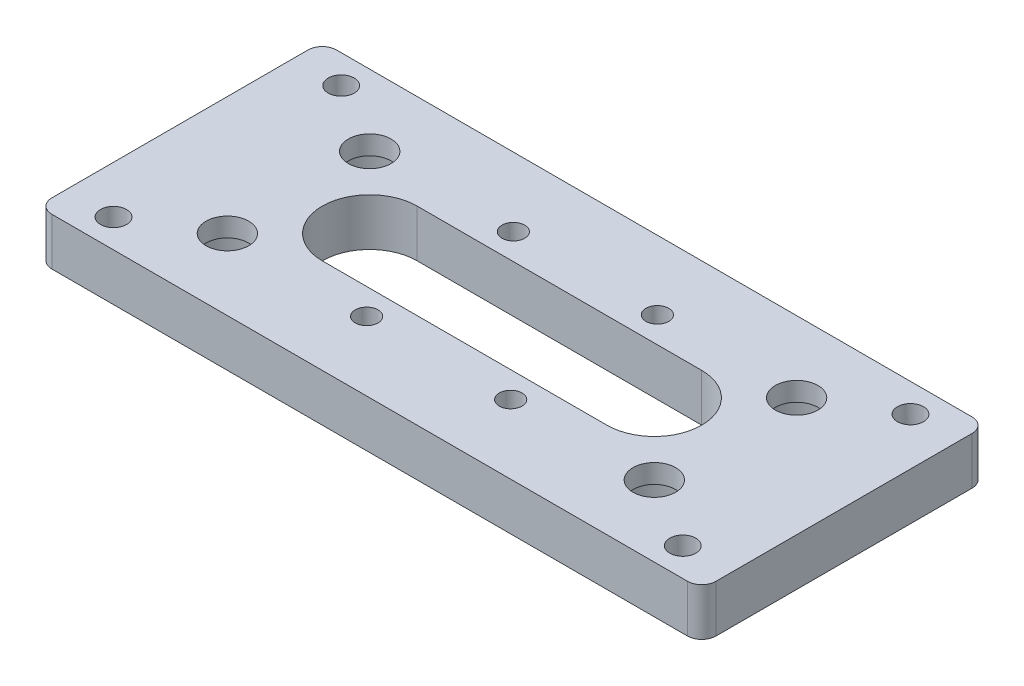
SolidWorks part; units mm, degrees
note: The reader was unsure of these and kept them because the rebuilt part matched: shared geometry of "Sketch1<2>".
ref_plane "Front Plane" through (0, 0, 0) normal (0, 0, 1) x (1, 0, 0)
ref_plane "Top Plane" through (0, 0, 0) normal (0, 1, 0) x (1, 0, 0)
ref_plane "Right Plane" through (0, 0, 0) normal (1, 0, 0) x (0, 0, -1)
sketch "Sketch1" plane through (0, 0, 0) normal (0, 1, 0) x (1, 0, 0)
  line L0 (65, -19) -> (65, 19) construction
  line L1 (-65, -19) -> (65, -19) construction
  line L2 (-65, 19) -> (-65, -19) construction
  line L3 (65, 19) -> (-65, 19) construction
  line L4 (67, 30) -> (-67, 30)
  line L5 (-70, 27) -> (-70, -27)
  line L6 (-67, -30) -> (67, -30)
  line L7 (70, -27) -> (70, 27)
  line L8 (67, 30) -> (-67, 30)
  line L9 (-70, 27) -> (-70, -27)
  line L10 (-67, -30) -> (67, -30)
  line L11 (70, -27) -> (70, 27)
  line L12 (65, -19) -> (65, 19)
  line L13 (-65, -19) -> (65, -19)
  line L14 (-65, 19) -> (-65, -19)
  line L15 (65, 19) -> (-65, 19)
  circle A0 centre (-60, 24) radius 2.75 construction
  circle A1 centre (-60, -24) radius 2.75 construction
  circle A2 centre (60, -24) radius 2.75 construction
  circle A3 centre (60, 24) radius 2.75 construction
  arc A4 (-67, 30) -> (-70, 27) centre (-67, 27) ccw
  arc A5 (-70, -27) -> (-67, -30) centre (-67, -27) ccw
  arc A6 (67, -30) -> (70, -27) centre (67, -27) ccw
  arc A7 (70, 27) -> (67, 30) centre (67, 27) ccw
  arc A8 (-67, 30) -> (-70, 27) centre (-67, 27) ccw
  arc A9 (-70, -27) -> (-67, -30) centre (-67, -27) ccw
  arc A10 (67, -30) -> (70, -27) centre (67, -27) ccw
  arc A11 (70, 27) -> (67, 30) centre (67, 27) ccw
  circle A12 centre (-60, 24) radius 2.75
  circle A13 centre (-60, -24) radius 2.75
  circle A14 centre (60, -24) radius 2.75
  circle A15 centre (60, 24) radius 2.75
  dimension "D1" = 0
extrude "Boss-Extrude1" add sketch "Sketch1" along normal blind 10
extrude "Boss-Extrude2" add sketch "Sketch1<2>" along normal blind 10
sketch "Sketch1<2>" plane through (0, 0, 0) normal (0, 1, 0) x (1, 0, 0) same geometry as "Sketch1"
hole_wizard "M3.5 Clearance Hole1" positions "Sketch2" profile "Sketch4" hole size "M3.5" standard "ANSI Metric"
sketch "Sketch2" plane through (0, 10, 0) normal (0, 1, 0) x (1, 0, 0)
  line L1 (15.1818, 15.4632) -> (-15.1818, 15.4632)
  line L2 (15.1818, 15.4632) -> (15.1818, -15.4632)
  line L3 (15.1818, -15.4632) -> (-15.1818, -15.4632)
  line L4 (-15.1818, 15.4632) -> (-15.1818, -15.4632)
  line L5 (15.1818, 15.4632) -> (-15.1818, -15.4632) construction
  line L6 (15.1818, -15.4632) -> (-15.1818, 15.4632) construction
  point P0 (0, 0)
  point P1 (-15.1818, -15.4632)
  point P16 (15.1818, 15.4632)
  point P17 (15.1818, -15.4632)
  point P18 (-15.1818, 15.4632)
sketch "Sketch4" plane through (0, 10, 0) normal (1, 0, 0) x (0, 0, 1)
  line L0 (0, 0) -> (0, 9.4421)
  line L1 (0, 9.4421) -> (2.4, 8)
  line L2 (2.4, 8) -> (2.4, 0)
  line L5 (2.4, 0) -> (0, 0)
  line L10 (0, 9.4421) -> (-2.4, 8) construction
  line L11 (0, -6.35) -> (0, 107.95) construction
  dimension "Hole Dia." = 4.8
  dimension "Hole Depth" = 8
  dimension "Drill Angle" = 118
sketch "Sketch5" plane through (0, 10, 0) normal (0, 1, 0) x (1, 0, 0)
  line L1 (-22.5, 22.5) -> (22.5, 22.5)
  line L2 (-22.5, 22.5) -> (-22.5, -22.5)
  line L3 (-22.5, -22.5) -> (22.5, -22.5)
  line L4 (22.5, 22.5) -> (22.5, -22.5)
  line L5 (-22.5, 22.5) -> (22.5, -22.5) construction
  line L6 (-22.5, -22.5) -> (22.5, 22.5) construction
  point P0 (0, 0)
  dimension "D1" = 45
  dimension "D2" = 45
sketch "Sketch6" plane through (0, 10, 0) normal (0, 1, 0) x (1, 0, 0)
  line L0 (-30, 0) -> (30, 0) construction
  line L1 (-30, 10) -> (30, 10)
  line L2 (-30, -10) -> (30, -10)
  arc A0 (-30, 10) -> (-30, -10) centre (-30, 0) ccw
  arc A1 (30, -10) -> (30, 10) centre (30, 0) ccw
  point P2 (0, 0)
  dimension "D1" = 20
  dimension "D2" = 60
extrude "Cut-Extrude1" cut sketch "Sketch6" against normal blind 10
hole_wizard "M16 Clearance Hole1" positions "Sketch7" profile "Sketch8" hole size "M16" standard "ANSI Metric"
sketch "Sketch7" plane through (0, 0, 0) normal (0, -1, 0) x (-1, 0, 0)
  line L1 (45, 15) -> (-45, 15)
  line L2 (45, 15) -> (45, -15)
  line L3 (45, -15) -> (-45, -15)
  line L4 (-45, 15) -> (-45, -15)
  line L5 (45, 15) -> (-45, -15) construction
  line L6 (45, -15) -> (-45, 15) construction
  point P1 (0, 0)
  point P2 (-45, -15)
  point P53 (45, 15)
  point P54 (45, -15)
  point P55 (-45, 15)
  dimension "D1" = 90
  dimension "D2" = 30
sketch "Sketch8" plane through (0, 0, 0) normal (1, 0, 0) x (0, 0, -1)
  line L0 (0, 0) -> (0, 6)
  line L1 (0, 6) -> (9.5, 6)
  line L2 (9.5, 6) -> (9.5, 0)
  line L5 (9.5, 0) -> (0, 0)
  line L10 (0, 6) -> (-9.5, 6) construction
  line L11 (0, -6.35) -> (0, 107.95) construction
  dimension "Hole Dia." = 19
  dimension "Hole Depth" = 6
  dimension "Drill Angle" = 180
hole_wizard "M8 Clearance Hole1" positions "Sketch11" profile "Sketch13" hole size "M8" standard "ANSI Metric" end condition through all
sketch "Sketch11" plane through (0, 0, 0) normal (0, -1, 0) x (-1, 0, 0)
  point P0 (45, -15)
  point P3 (45, 15)
  point P6 (-45, 15)
  point P9 (-45, -15)
  point P15 (0, 0)
sketch "Sketch13" plane through (-45, 0, 15) normal (1, 0, 0) x (0, 0, -1)
  line L0 (0, 0) -> (0, 10)
  line L1 (0, 10) -> (4.5, 10)
  line L2 (4.5, 10) -> (4.5, 0)
  line L5 (4.5, 0) -> (0, 0)
  line L11 (0, -6.35) -> (0, 107.95) construction
  dimension "Thru Hole Dia." = 9
  dimension "Thru Hole Depth" = 10
